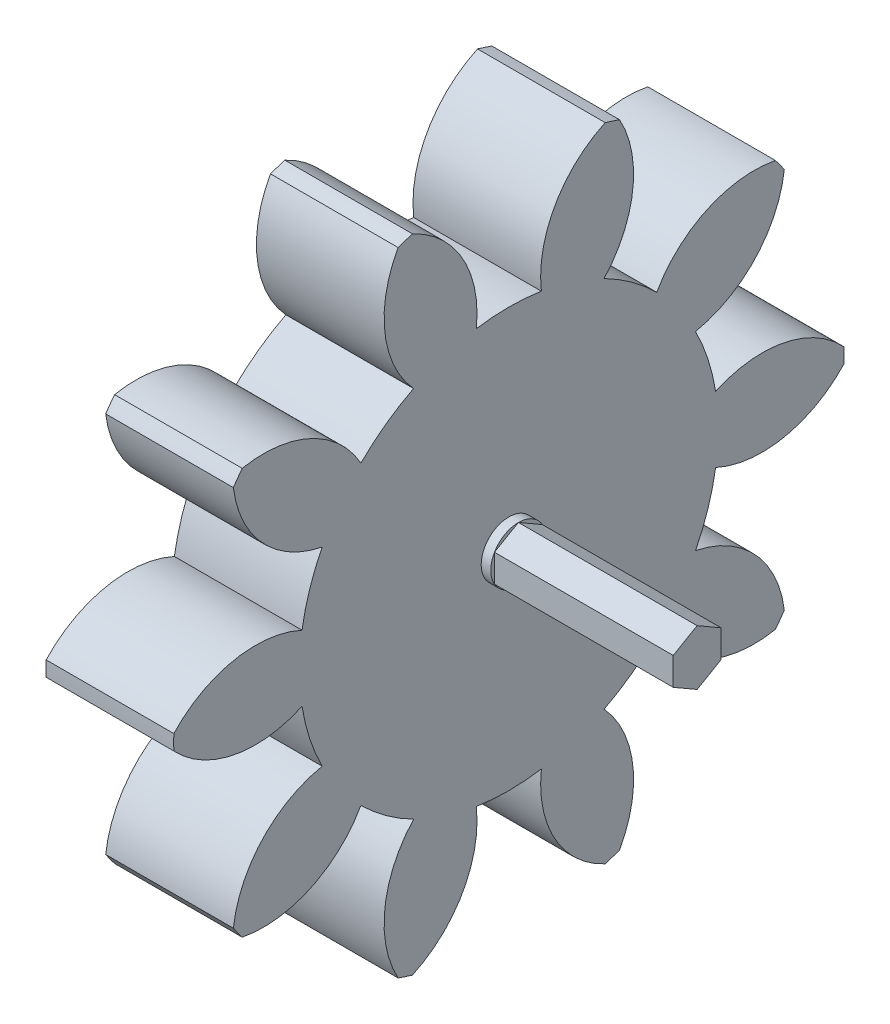
SolidWorks part; units mm, degrees
ref_plane "Plane1" through (0, 0, 0) normal (0, 0, 1) x (1, 0, 0)
ref_plane "Plane2" through (0, 0, 0) normal (0, 1, 0) x (1, 0, 0)
ref_plane "Plane3" through (0, 0, 0) normal (1, 0, 0) x (0, 0, -1)
other "Configuration Table"
sketch "HoldingSke" plane through (0, 0, 0) normal (0, 1, 0) x (1, 0, 0)
  line L0 (0, 0) -> (0.5627, -0.0992)
  line L1 (-15, 0) -> (100, 0) construction
  line L2 (0, 0) -> (-2.1039, 2.3779)
  line L3 (0, 0) -> (-11.863, 4.5341)
  line L4 (0, 0) -> (8.5048, 1.4996)
  line L5 (0, 0) -> (-46.8476, -17.4728)
  line L6 (0, 0) -> (-3.3159, -2.2372)
  line L7 (-2.1039, 2.3779) -> (8.6586, 51.2059)
  line L8 (-76.2, 54.61) -> (-76.1, 54.61)
  line L9 (-71.009, 38.7566) -> (-53.1078, 45.2721)
  line L10 (-76.2, 71.12) -> (104.1128, 71.12)
  line L11 (0, 0) -> (-4, 0)
  line L12 (-76.2, 101.6) -> (-76.147, 101.6)
  line L13 (24.9733, 27.94) -> (52.9518, 28.4284)
  line L14 (24.9733, 27.94) -> (24.9743, 27.94)
  line L15 (24.9733, 27.94) -> (100.4006, 29.5858)
  line L16 (-63.627, -1.75) -> (-12.827, -1.75)
  circle A0 centre (0, 0) radius 0.5
  circle A1 centre (0, 0) radius 6.5615
  circle A2 centre (0, 0) radius 37.5
  circle A3 centre (0, 0) radius 0.5
  dimension "MHD" = 13.123
  dimension "Hub_dia" = 75
  dimension "Bore" = 1
  dimension "MBD" = 1
  dimension "Num_teeth" = 10
  dimension "Pitch" = 0.5714
  dimension "Overall_len" = 50
  dimension "Show_teeth" = 10
  dimension "Thickness" = 4
  dimension "OAL" = 50.0001
  dimension "T_dim" = 0.1
  dimension "Ap" = 20
  dimension "H" = 19.05
  dimension "Pitch_radius" = 180.3128
  dimension "Width" = 4
  dimension "Backlash" = 0.053
  dimension "Addendum_fac" = 1
  dimension "Dedendum_fac" = 1.25
  dimension "Clearance_fac" = 0.25
  dimension "Dedendum_add" = 0.001
  dimension "Module" = 1.75
sketch "BasProSke" plane through (0, 0, 0) normal (0, 1, 0) x (1, 0, 0)
  line L0 (-10, 0) -> (60, 0) construction
  line L1 (0, 0) -> (0, 10.5)
  line L2 (0, 0) -> (4, 0)
  line L3 (4, 0) -> (4, 10.5)
  line L4 (4, 10.5) -> (0, 10.5)
  dimension "Thickness" = 4
  dimension "Diameter" = 21
revolve "Base-Revolve" add sketch "BasProSke" angle 360 about L0
sketch "TooCutSke" plane through (0, 0, 0) normal (1, 0, 0) x (0, 0, -1)
  line L1 (0, 0) -> (0, 107) construction
  line L2 (0, 0) -> (-1.4614, 8.6271) construction
  line L3 (0, 0) -> (-5.35, 16.4656) construction
  line L4 (-1.4614, 8.6271) -> (-2.675, 8.2328) construction
  arc A0 (1.0196, 6.4818) -> (-1.0196, 6.4818) centre (0, 0) ccw
  arc A1 (3.0536, 10.0727) -> (-3.0536, 10.0727) centre (0, 0) ccw
  circle A2 centre (0, 0) radius 8.75 construction
  circle A3 centre (0, 0) radius 8.2223 construction
  arc A4 (-1.0196, 6.4818) -> (-3.0536, 10.0727) centre (-4.4964, 6.8839) ccw
  arc A5 (3.0536, 10.0727) -> (1.0196, 6.4818) centre (4.4964, 6.8839) ccw
  dimension "Root_dia" = 13.123
  dimension "Overcut_dia" = 21.0508
  dimension "Pitch_dia" = 17.5
  dimension "Base_dia" = 16.4446
  dimension "Flank_rad" = 3.5
  dimension "Half_ang" = 18
  dimension "Half_CT" = 1.2761
extrude "ToothCut" cut sketch "TooCutSke" along normal through all
fillet "Breaks" [suppressed] radius 0.035 tangent propagation no
fillet "RootFillets" [suppressed] radius 0.4385
pattern_circular "TeethCuts" count 10 every 36 about axis through (-10, 0, 0) along (1, 0, 0) of "ToothCut", "RootFillets", "Breaks"
sketch "HubNeaOneSke" plane through (0, 0, 0) normal (-1, 0, 0) x (0, 0, 1)
  circle A0 centre (0, 0) radius 6.5615
  dimension "Diameter" = 13.123
extrude "HubNearOne" [suppressed] add sketch "HubNeaOneSke" along normal blind 46.0001
sketch "HubNeaBotSke" plane through (0, 0, 0) normal (-1, 0, 0) x (0, 0, 1)
  circle A0 centre (0, 0) radius 6.5615
  dimension "Diameter" = 13.123
extrude "HubNearBoth" [suppressed] add sketch "HubNeaBotSke" along normal blind 23
ref_plane "FarPln" through (4, 0, 0) normal (1, 0, 0) x (0, 0, -1)
sketch "HubFarSke" plane through (4, 0, 0) normal (1, 0, 0) x (0, 0, -1)
  circle A0 centre (0, 0) radius 6.5615
  dimension "Diameter" = 13.123
extrude "HubFar" [suppressed] add sketch "HubFarSke" along normal blind 23
sketch "BorSke" plane through (0, 0, 0) normal (1, 0, 0) x (0, 0, -1)
  circle A0 centre (0, 0) radius 0.5
  dimension "Diameter" = 1
extrude "Bore" cut sketch "BorSke" along normal mid plane 100.0001
sketch "KeySke" plane through (0, 0, 0) normal (1, 0, 0) x (0, 0, -1)
  line L0 (-0.05, 0) -> (-0.05, 0.6)
  line L1 (-0.05, 0.6) -> (0.05, 0.6)
  line L2 (0.05, 0.6) -> (0.05, 0)
  line L3 (0, 0) -> (0, 34) construction
  line L4 (-0.05, 0) -> (0.05, 0)
  dimension "Offset" = 0.6
  dimension "Width" = 0.1
extrude "Keyway" [suppressed] cut sketch "KeySke" along normal mid plane 100.0001
pattern_circular "Keyway2" [suppressed] count 2 every 90 about axis through (-10, 0, 0) along (1, 0, 0)
sketch "Sketch2" plane through (0, 0, 0) normal (-1, 0, 0) x (0, 0, 1)
  line L1 (0.75, 0.433) -> (0, 0.866)
  line L2 (0, 0.866) -> (-0.75, 0.433)
  line L3 (-0.75, 0.433) -> (-0.75, -0.433)
  line L4 (-0.75, -0.433) -> (0, -0.866)
  line L5 (0, -0.866) -> (0.75, -0.433)
  line L6 (0.75, -0.433) -> (0.75, 0.433)
  circle A0 centre (0, 0) radius 0.75 construction
  circle A1 centre (0, 0) radius 0.866
  circle M8 centre (0, 0) radius 0.5
  dimension "D1" = 1.5
extrude "Boss-Extrude1" add sketch "Sketch2" against normal blind 4.3 contours L4 A1 | L5 L6 L1 L2 L3 L4 M8 | L3 A1 | L2 A1 | L1 A1 | L6 A1 | L5 A1 | M8 region at (0, 0, 0.7271) region at (0, 0, 0.7967) region at (0, 0.69, 0.3983) region at (0, 0.69, -0.3983) region at (0, -0.69, 0.3983) region at (0, 0, -0.7967) region at (0, -0.69, -0.3983) region at (0, 0, 0)
extrude "Boss-Extrude2" add sketch "Sketch2<3>" against normal blind 9.9 contours L5 L6 L1 L2 L3 L4 M8 | M8 region at (0, 0, 0.7271) region at (0, 0, 0)
sketch "Sketch2<3>" plane through (0, 0, 0) normal (-1, 0, 0) x (0, 0, 1) same geometry as "Sketch2"
equation "' \"Module@HoldingSke\" = 6.35"
equation "' \"Num_teeth@HoldingSke\" = 12"
equation "' \"Ap@HoldingSke\" =  20"
equation "' \"Ap@HoldingSke\" = 20"
equation "' \"Width@HoldingSke\" = 0.5 * 25.4"
equation "' \"Hub_dia@HoldingSke\"= 1 * 25.4"
equation "' \"Hub_dia@HoldingSke\" = 1 * 25.4"
equation "' \"Overall_len@HoldingSke\" = 1.0 * 25.4"
equation "' \"Bore@HoldingSke\" = 0.75 * 25.4"
equation "' \"T_dim@HoldingSke\" = 0.1 * 25.4"
equation "' \"Width@KeySke\" = 0.25 * 25.4"
equation "' \"Show_teeth@HoldingSke\" = 13"
equation "' \"Backlash@HoldingSke\" = 0.009 * 25.4"
equation "' \"Addendum_fac@HoldingSke\" = 1.0"
equation "' \"Dedendum_fac@HoldingSke\" = 1.25"
equation "' \"Dedendum_add@HoldingSke\" = 0.00005 * 25.4"
equation "' \"Clearance_fac@HoldingSke\" = 0.25"
equation "\"Pitch@HoldingSke\" = 1 / \"Module@HoldingSke\""
equation "\"Overcut_dia@TooCutSke\" = (\"Num_teeth@HoldingSke\" + 2 * \"Addendum_fac@HoldingSke\") / \"Pitch@HoldingSke\" + 0.002 * 25.4"
equation "\"Pitch_dia@TooCutSke\" = \"Num_teeth@HoldingSke\" / \"Pitch@HoldingSke\""
equation "\"Base_dia@TooCutSke\" = \"Num_teeth@HoldingSke\" / \"Pitch@HoldingSke\" * cos((\"Ap@HoldingSke\"  * 3.14159265 / 180))"
equation "\"Root_dia@TooCutSke\" = (\"Num_teeth@HoldingSke\" + 2) / \"Pitch@HoldingSke\" - 2 * (\"Addendum_fac@HoldingSke\" + \"Dedendum_fac@HoldingSke\") / \"Pitch@HoldingSke\" - \"Dedendum_add@HoldingSke\" * 2"
equation "\"Half_ang@TooCutSke\" = 180 / \"Num_teeth@HoldingSke\""
equation "\"Half_CT@TooCutSke\" = \"Num_teeth@HoldingSke\" / \"Pitch@HoldingSke\" * sin((3.14159265 / 2 / \"Num_teeth@HoldingSke\")) / 2 - 7 * \"Backlash@HoldingSke\" / 4"
equation "\"Flank_rad@TooCutSke\" = \"Num_teeth@HoldingSke\" / \"Pitch@HoldingSke\" / 5"
equation "\"Radius@RootFillets\" = \"Clearance_fac@HoldingSke\" / \"Pitch@HoldingSke\" + \"Dedendum_add@HoldingSke\""
equation "\"Break_rad@Breaks\" = 0.02 / \"Pitch@HoldingSke\""
equation "\"Thickness@HoldingSke\" = \"Width@HoldingSke\""
equation "\"OAL@HoldingSke\" = \"Thickness@HoldingSke\""
equation "\"MHD@HoldingSke\" = (\"Num_teeth@HoldingSke\" + 2) / \"Pitch@HoldingSke\" - 2 * (\"Addendum_fac@HoldingSke\" + \"Dedendum_fac@HoldingSke\")  / \"Pitch@HoldingSke\" - \"Dedendum_add@HoldingSke\" * 2"
equation "\"MBD@HoldingSke\" = (\"Num_teeth@HoldingSke\" + 2) / \"Pitch@HoldingSke\" - 2 * (\"Addendum_fac@HoldingSke\" + \"Dedendum_fac@HoldingSke\")  / \"Pitch@HoldingSke\" - \"Dedendum_add@HoldingSke\" * 2 - 0.002 * 25.4"
equation "\"MHD@HoldingSke\" = ((sgn( \"MHD@HoldingSke\" - \"Hub_dia@HoldingSke\" )-1)*( \"MHD@HoldingSke\" - \"Hub_dia@HoldingSke\" ))/-2+ \"Hub_dia@HoldingSke\""
equation "\"MBD@HoldingSke\" = ((sgn( \"MBD@HoldingSke\" - \"Bore@HoldingSke\" )-1)*( \"MBD@HoldingSke\" - \"Bore@HoldingSke\" ))/-2+ \"Bore@HoldingSke\""
equation "\"OAL@HoldingSke\" = ((sgn( \"OAL@HoldingSke\" - \"Overall_len@HoldingSke\" )+1)*( \"OAL@HoldingSke\" - \"Overall_len@HoldingSke\" ))/2 + \"Overall_len@HoldingSke\" + 0.000002 * 25.4"
equation "\"Num_teeth@TeethCuts\" = int( \"Show_teeth@HoldingSke\" ) + 1"
equation "\"Num_teeth@TeethCuts\" = ((sgn( \"Num_teeth@TeethCuts\" - \"Num_teeth@HoldingSke\" )-1)*( \"Num_teeth@TeethCuts\" - \"Num_teeth@HoldingSke\" ))/-2+ \"Num_teeth@HoldingSke\""
equation "\"Num_teeth@TeethCuts\" = ((sgn( \"Num_teeth@TeethCuts\" - 2.0)+1)*( \"Num_teeth@TeethCuts\" - 2.0))/2 +2.0"
equation "\"Angle@TeethCuts\" = 360.0 / \"Num_teeth@HoldingSke\""
equation "\"Diameter@BasProSke\" = (\"Num_teeth@HoldingSke\" + 2 * \"Addendum_fac@HoldingSke\") / \"Pitch@HoldingSke\""
equation "\"Thickness@BasProSke\"  = \"Thickness@HoldingSke\""
equation "' \"Fillet_rad@BasProSke\" =  \"Thickness@HoldingSke\" * 0.05"
equation "' \"Fillet_rad@BasProSke\" = \"Thickness@HoldingSke\" * 0.05"
equation "\"MHD@HoldingSke\" = ((sgn( \"MHD@HoldingSke\" - \"Root_dia@TooCutSke\" )-1)*( \"MHD@HoldingSke\" - \"Root_dia@TooCutSke\" ))/-2+ \"Root_dia@TooCutSke\""
equation "\"Diameter@HubNeaOneSke\" = \"MHD@HoldingSke\""
equation "\"Length@HubNearOne\" = \"OAL@HoldingSke\" - \"Thickness@BasProSke\""
equation "\"Diameter@HubNeaBotSke\" = \"MHD@HoldingSke\""
equation "\"Length@HubNearBoth\" = ( \"OAL@HoldingSke\" - \"Thickness@BasProSke\" ) / 2.0"
equation "\"Thickness@FarPln\" = \"Thickness@BasProSke\""
equation "\"Diameter@HubFarSke\" = \"MHD@HoldingSke\""
equation "\"Length@HubFar\" = ( \"OAL@HoldingSke\" - \"Thickness@BasProSke\" ) / 2.0"
equation "\"Diameter@BorSke\" = \"MBD@HoldingSke\""
equation "\"D1@Bore\" = \"OAL@HoldingSke\" * 2.0"
equation "\"D1@Keyway\" = \"OAL@HoldingSke\" * 2.0"
equation "\"Offset@KeySke\" = \"T_dim@HoldingSke\" + \"MBD@HoldingSke\" / 2.0"
